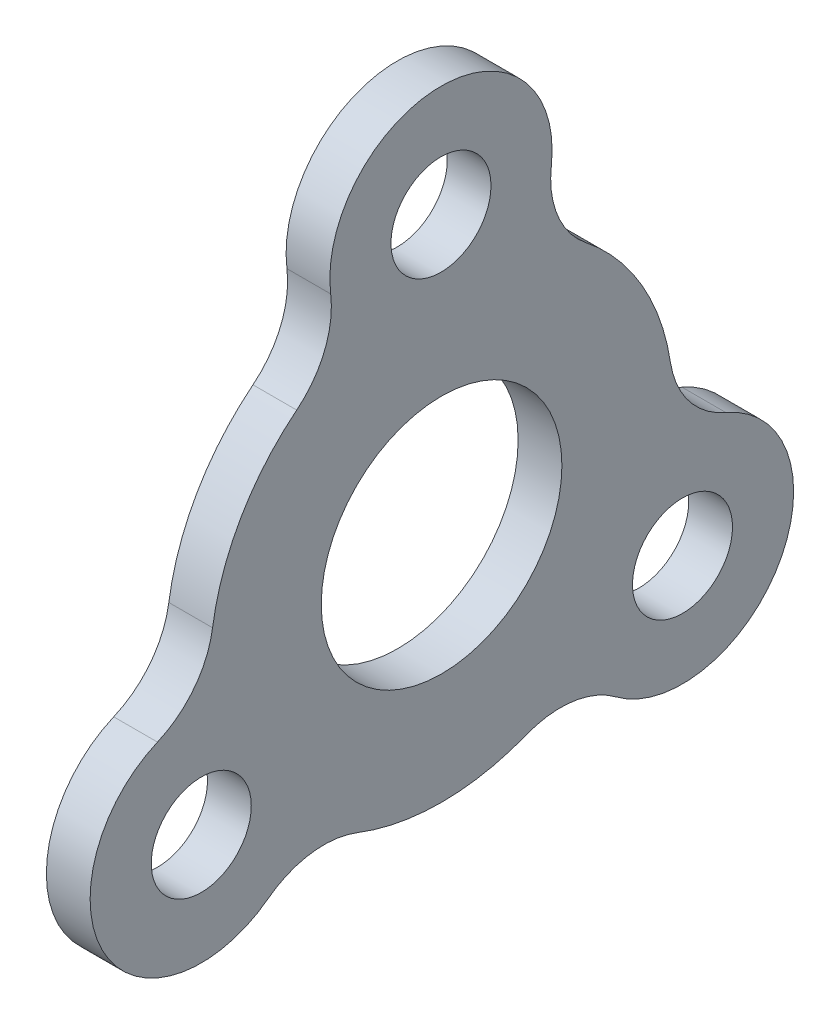
SolidWorks part; units mm, degrees
material "AR500"
ref_plane "Front Plane" through (0, 0, 0) normal (0, 0, 1) x (1, 0, 0)
ref_plane "Top Plane" through (0, 0, 0) normal (0, 1, 0) x (1, 0, 0)
ref_plane "Right Plane" through (0, 0, 0) normal (1, 0, 0) x (0, 0, -1)
sketch "Sketch1" plane through (0, 0, 0) normal (1, 0, 0) x (0, 0, -1)
  line L1 (-0.0412, 19.05) -> (-16.4771, -9.5607) construction
  line L2 (-16.4771, -9.5607) -> (16.5183, -9.4893) construction
  line L3 (16.5183, -9.4893) -> (-0.0412, 19.05) construction
  circle A0 centre (0, 0) radius 8.25
  arc A1 (-9.9327, 12.3837) -> (-15.7013, 2.3422) centre (0, 0) ccw
  circle A2 centre (-0.0412, 19.05) radius 3.429
  circle A3 centre (-16.4771, -9.5607) radius 3.429
  circle A4 centre (16.5183, -9.4893) radius 3.429
  arc A6 (-15.7013, 2.3422) -> (-19.4797, -2.5571) centre (-21.9818, 3.2791) cw
  arc A7 (-19.4797, -2.5571) -> (-11.8868, -15.6429) centre (-16.4771, -9.5607) ccw
  arc A8 (-11.8868, -15.6429) -> (-5.7583, -14.7939) centre (-8.0616, -20.7114) cw
  circle A9 centre (0, 0) radius 19.05 construction
  arc A10 (9.8791, 12.4266) -> (7.5253, 18.1485) centre (13.8307, 17.3972) cw
  arc A11 (7.5253, 18.1485) -> (-7.6037, 18.1157) centre (-0.0412, 19.05) ccw
  arc A12 (-7.6037, 18.1157) -> (-9.9327, 12.3837) centre (-13.9058, 17.3372) cw
  arc A13 (5.8222, -14.7688) -> (11.9544, -15.5913) centre (8.1511, -20.6763) cw
  arc A14 (11.9544, -15.5913) -> (19.4905, -2.4729) centre (16.5183, -9.4893) ccw
  arc A15 (19.4905, -2.4729) -> (15.691, 2.4101) centre (21.9674, 3.3742) cw
  arc A17 (15.691, 2.4101) -> (9.8791, 12.4266) centre (0, 0) ccw
  arc A19 (-5.7583, -14.7939) -> (5.8222, -14.7688) centre (0, 0) ccw
  circle A20 centre (-0.0412, 19.05) radius 2.5527 construction
  point P3 (-8.0182, 17.4625)
  point P17 (0, 0)
  point P19 (7.3273, 11.8429)
  point P20 (10.0609, 12.9208)
  point P35 (0, 0)
  point P36 (0, 0)
  point P39 (0, 0)
  dimension "D3" = 16.5
  dimension "D4" = 6.858
  dimension "D5" = 7.62
  dimension "D6" = 6.35
  dimension "D7" = 15.875
  dimension "D2" = 3
extrude "Boss-Extrude1" add sketch "Sketch1" along normal blind 3
equation "\"D3@Sketch1\"=16.5mm"
